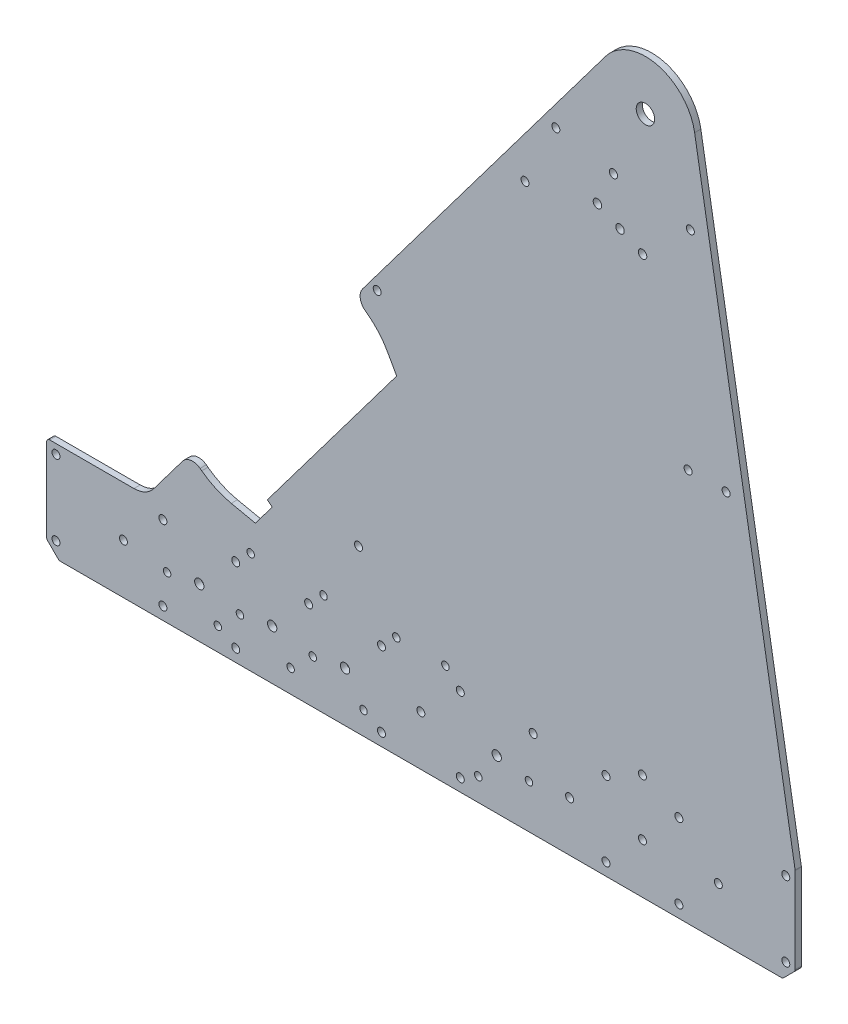
SolidWorks part; units mm, degrees
ref_plane "Front Plane" through (0, 0, 0) normal (0, 0, 1) x (1, 0, 0)
ref_plane "Top Plane" through (0, 0, 0) normal (0, 1, 0) x (1, 0, 0)
ref_plane "Right Plane" through (0, 0, 0) normal (1, 0, 0) x (0, 0, -1)
sketch "Sketch1" plane through (0, 0, 0) normal (0, 0, 1) x (1, 0, 0)
  line L1 (0, 0) -> (381, 0)
  line L2 (0, 0) -> (0, 50.8)
  line L4 (381, 0) -> (381, 50.8)
  line L5 (381, 50.8) -> (329.8374, 350.3513)
  line L6 (0, 50.8) -> (44.463, 50.8)
  line L7 (54.6105, 55.8634) -> (73.025, 80.3327)
  line L9 (112.3265, 79.755) -> (178.1676, 167.245)
  line L11 (157.0275, 191.9556) -> (284.5049, 361.3482)
  line L12 (112.3265, 79.755) -> (114.8634, 77.8458)
  line L13 (114.8634, 77.8458) -> (106.2722, 66.4299)
  line L14 (157.0275, 191.9556) -> (169.7119, 182.4098)
  line L15 (169.7119, 182.4098) -> (178.1676, 167.245)
  line L16 (73.025, 80.3327) -> (85.7094, 70.7869)
  line L17 (85.7094, 70.7869) -> (106.2722, 66.4299)
  line L18 (169.7119, 182.4098) -> (85.7094, 70.7869) construction
  arc A0 (284.5049, 361.3482) -> (329.8374, 350.3513) centre (304.8, 346.075) cw
  arc A1 (44.463, 50.8) -> (54.6105, 55.8634) centre (44.463, 63.5) ccw
  point P11 (50.8, 50.8)
  dimension "D4" = 346.075
  dimension "D7" = 12.7
  dimension "D5" = 25.4
  dimension "D1" = 50.8
  dimension "D2" = 381
  dimension "D3" = 76.2
  dimension "D6" = 50.8
  dimension "D8" = 123.825
  dimension "D9" = 139.7
  dimension "D10" = 15.875
  dimension "D11" = 31.75
  dimension "D12" = 73.025
  dimension "D13" = 3.175
  dimension "D14" = 14.2875
  dimension "D15" = 115
extrude "Boss-Extrude1" add sketch "Sketch1" along normal blind 3.175
sketch "Sketch2" plane through (0, 0, 3.175) normal (0, 0, 1) x (1, 0, 0)
  line L1 (190.5, 50.8) -> (190.5, 0) construction
  line L3 (0, 0) -> (381, 0) construction
  line L5 (0, 6.35) -> (0, 0)
  line L6 (0, 50.8) -> (0, 0) construction
  line L7 (0, 0) -> (6.35, 0)
  line L8 (6.35, 0) -> (0, 6.35)
  line L9 (381, 0) -> (374.65, 0)
  line L10 (374.65, 0) -> (381, 6.35)
  line L11 (381, 6.35) -> (381, 0)
  circle A19 centre (4.7625, 46.0375) radius 2.032
  circle A20 centre (4.7625, 7.9375) radius 2.032
  circle A21 centre (376.2375, 7.9375) radius 2.032
  circle A22 centre (376.2375, 46.0375) radius 2.032
  dimension "D21" = 6.35
  dimension "D27" = 4.064
  dimension "D4" = 46.0375
  dimension "D22" = 6.35
  dimension "D25" = 4.7625
  dimension "D28" = 7.9375
extrude "Cut-Extrude1" cut sketch "Sketch2" against normal up to next
sketch "Sketch5" plane through (0, 0, 3.175) normal (0, 0, 1) x (1, 0, 0)
  line L0 (151.892, 25.4) -> (229.108, 25.4) construction
  line L1 (229.108, 25.4) -> (341.884, 25.4) construction
  circle A0 centre (39.116, 25.4) radius 2.032
  circle A1 centre (59.182, 6.35) radius 2.032
  circle A2 centre (59.182, 44.45) radius 2.032
  circle A3 centre (96.266, 44.45) radius 2.032
  circle A4 centre (133.35, 44.45) radius 2.032
  circle A5 centre (170.434, 44.45) radius 2.032
  circle A6 centre (210.566, 44.45) radius 2.032
  circle A7 centre (210.566, 6.35) radius 2.032
  circle A8 centre (170.434, 6.35) radius 2.032
  circle A9 centre (247.65, 44.45) radius 2.032
  circle A10 centre (266.192, 25.4) radius 2.032
  circle A11 centre (39.116, 25.4) radius 2.286 construction
  circle A12 centre (59.182, 44.45) radius 1.905 construction
  circle A13 centre (59.182, 6.35) radius 1.905 construction
  circle A14 centre (96.266, 44.45) radius 1.905 construction
  circle A15 centre (133.35, 44.45) radius 1.905 construction
  circle A16 centre (170.434, 44.45) radius 1.905 construction
  circle A17 centre (170.434, 6.35) radius 2.159 construction
  circle A18 centre (210.566, 6.35) radius 2.159 construction
  circle A19 centre (210.566, 44.45) radius 1.905 construction
  circle A20 centre (247.65, 44.45) radius 1.905 construction
  circle A21 centre (266.192, 25.4) radius 2.286 construction
  circle A22 centre (77.724, 25.4) radius 2.3813
  circle A23 centre (114.808, 25.4) radius 2.3813
  circle A24 centre (151.892, 25.4) radius 2.3813
  circle A25 centre (229.108, 25.4) radius 2.3813
  circle A26 centre (190.5, 25.4) radius 2.032
  circle A28 centre (303.276, 25.4) radius 2.032
  circle A29 centre (341.884, 25.4) radius 2.032
  circle A30 centre (77.724, 25.4) radius 7.366 construction
  circle A31 centre (114.808, 25.4) radius 7.366 construction
  circle A32 centre (151.892, 25.4) radius 7.366 construction
  circle A33 centre (229.108, 25.4) radius 7.366 construction
  dimension "D1" = 4.064
  dimension "D2" = 4.7625
  dimension "D3" = 37.084
  dimension "D4" = 38.608
  dimension "D5" = 38.608
extrude "Cut-Extrude4" cut sketch "Sketch5" against normal through all
sketch "Sketch6" plane through (0, 0, 3.175) normal (0, 0, 1) x (1, 0, 0)
  line L0 (6.35, 0) -> (374.65, 0) construction
  line L1 (266.192, 25.4) -> (303.276, 25.4) construction
  line L2 (284.734, 6.35) -> (284.734, 44.45) construction
  line L3 (151.892, 25.4) -> (114.808, 25.4) construction
  line L4 (114.808, 25.4) -> (77.724, 25.4) construction
  circle A0 centre (284.734, 44.45) radius 2.032
  circle A1 centre (284.734, 6.35) radius 2.032
  circle A2 centre (321.818, 6.35) radius 2.032
  circle A3 centre (321.818, 44.45) radius 2.032
  circle A4 centre (96.266, 6.35) radius 2.032
  circle A6 centre (303.276, 53.975) radius 2.032
  arc A7 (304.329, 52.3875) -> (302.223, 52.3875) centre (303.276, 53.975) ccw construction
  point P8 (284.734, 25.4)
  point P9 (284.734, 25.4)
  point P28 (96.266, 25.4)
  dimension "D1" = 4.064
  dimension "D2" = 6.35
  dimension "D3" = 37.084
extrude "Cut-Extrude5" cut sketch "Sketch6" against normal through all
sketch "Sketch3" plane through (0, 0, 3.175) normal (0, 0, 1) x (1, 0, 0)
  line L0 (73.025, 80.3327) -> (54.6105, 55.8634) construction
  line L1 (381, 6.35) -> (381, 50.8) construction
  line L2 (6.35, 0) -> (374.65, 0) construction
  line L3 (304.8, 346.075) -> (288.5131, 311.6316) construction
  line L4 (280.3697, 294.4099) -> (288.5131, 311.6316) construction
  line L5 (280.3697, 294.4099) -> (291.8508, 288.9809) construction
  line L6 (291.8508, 288.9809) -> (303.3319, 283.552) construction
  line L7 (381, 50.8) -> (329.8374, 350.3513) construction
  line L9 (0, 50.8) -> (0, 6.35) construction
  line L12 (284.5049, 361.3482) -> (157.0275, 191.9556) construction
  circle A0 centre (304.8, 346.075) radius 4.699
  circle A1 centre (168.275, 200.025) radius 2.032
  circle A2 centre (158.75, 82.55) radius 2.032
  circle A3 centre (288.5131, 311.6316) radius 2.0955
  circle A5 centre (280.3697, 294.4099) radius 2.159
  circle A6 centre (291.8508, 288.9809) radius 2.159
  circle A7 centre (303.3319, 283.552) radius 2.159
  circle A8 centre (327.6754, 306.4341) radius 2.032
  circle A9 centre (345.8498, 200.025) radius 2.032
  circle A12 centre (259.2118, 317.1783) radius 2.032
  circle A13 centre (326.524, 200.025) radius 2.032
  circle A25 centre (243.5076, 285.75) radius 2.032
  dimension "D1" = 9.398
  dimension "D3" = 4.064
  dimension "D6" = 4.064
  dimension "D11" = 4.318
  dimension "D10" = 4.191
  dimension "D13" = 4.064
  dimension "D20" = 4.064
  dimension "D19" = 4.064
  dimension "D4" = 222.25
  dimension "D5" = 82.55
  dimension "D7" = 19.05
  dimension "D8" = 12.7
  dimension "D9" = 38.1
  dimension "D12" = 12.7
  dimension "D14" = 9.525
  dimension "D15" = 9.525
  dimension "D16" = 107.95
  dimension "D17" = 200.025
  dimension "D23" = 53.975
  dimension "D24" = 6.35
  dimension "D25" = 200.025
  dimension "D26" = 168.275
  dimension "D27" = 28.575
  dimension "D29" = 12.7
  dimension "D30" = 35
  dimension "D31" = 180
  dimension "D32" = 285.75
extrude "Cut-Extrude2" cut sketch "Sketch3" against normal through all
fillet "Fillet1" radius 1.5875 6 edges at (374.65, 0, 1.5875) (381, 6.35, 1.5875) (381, 50.8, 1.5875) (6.35, 0, 1.5875) (0, 6.35, 1.5875) (0, 50.8, 1.5875)
sketch "Sketch4" plane through (0, 0, 0) normal (0, 0, -1) x (-1, 0, 0)
  circle A0 centre (-61.3181, 22.2981) radius 1.905 construction
  circle A1 centre (-87.1313, 11.606) radius 1.905 construction
  circle A2 centre (-98.4021, 22.2981) radius 1.905 construction
  circle A3 centre (-124.2153, 11.606) radius 1.905 construction
  circle A4 centre (-135.4861, 22.2981) radius 1.905 construction
  circle A5 centre (-161.2993, 11.606) radius 1.905 construction
  circle A6 centre (-245.5139, 22.2981) radius 1.905 construction
  circle A7 centre (-219.7007, 11.606) radius 1.905 construction
  circle A8 centre (-202.982, 51.9684) radius 1.905 construction
  circle A9 centre (-178.018, 51.9684) radius 1.905 construction
  circle A10 centre (-140.934, 51.9684) radius 1.905 construction
  circle A11 centre (-103.85, 51.9684) radius 1.905 construction
  circle A12 centre (-61.3181, 22.2981) radius 1.905
  circle A13 centre (-87.1313, 11.606) radius 1.905
  circle A14 centre (-98.4021, 22.2981) radius 1.905
  circle A15 centre (-124.2153, 11.606) radius 1.905
  circle A16 centre (-135.4861, 22.2981) radius 1.905
  circle A17 centre (-161.2993, 11.606) radius 1.905
  circle A18 centre (-245.5139, 22.2981) radius 1.905
  circle A19 centre (-219.7007, 11.606) radius 1.905
  circle A20 centre (-202.982, 51.9684) radius 1.905
  circle A21 centre (-178.018, 51.9684) radius 1.905
  circle A22 centre (-140.934, 51.9684) radius 1.905
  circle A23 centre (-103.85, 51.9684) radius 1.905
extrude "Cut-Extrude3" cut sketch "Sketch4" against normal up to next
fillet "Fillet2" radius 38.1 2 edges at (85.7094, 70.7869, 1.5875) (169.7119, 182.4098, 1.5875)
fillet "Fillet3" radius 6.35 2 edges at (73.025, 80.3327, 1.5875) (157.0275, 191.9556, 1.5875)
